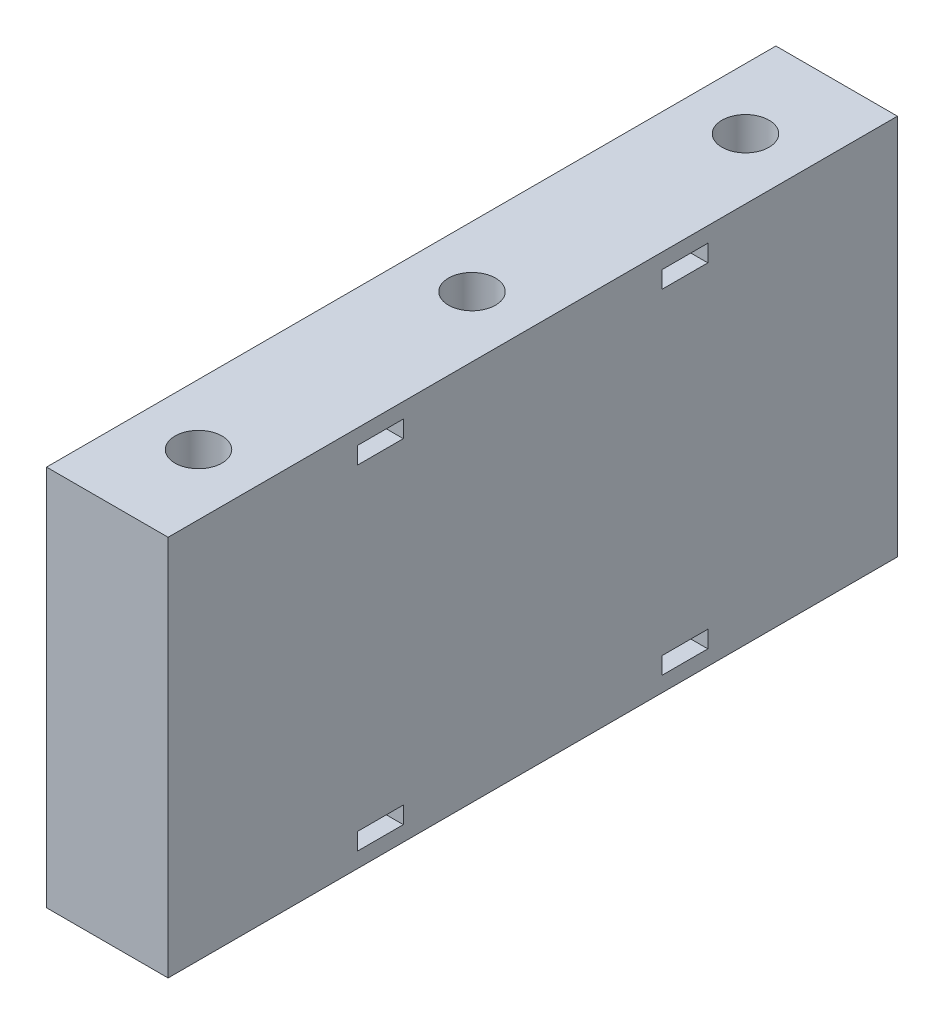
SolidWorks part; units mm, degrees
ref_plane "Front" through (0, 0, 0) normal (0, 0, 1) x (1, 0, 0)
ref_plane "Top" through (0, 0, 0) normal (0, 1, 0) x (1, 0, 0)
ref_plane "Right" through (0, 0, 0) normal (1, 0, 0) x (0, 0, -1)
sketch "Sketch1" plane through (0, 0, 0) normal (1, 0, 0) x (0, 0, -1)
  line L1 (-38.1, -19.939) -> (38.1, -19.939)
  line L2 (-38.1, -19.939) -> (-38.1, 19.939)
  line L3 (-38.1, 19.939) -> (38.1, 19.939)
  line L4 (38.1, -19.939) -> (38.1, 19.939)
  line L5 (-38.1, -19.939) -> (38.1, 19.939) construction
  line L6 (-38.1, 19.939) -> (38.1, -19.939) construction
  point P0 (0, 0)
  dimension "D1" = 39.878
  dimension "D2" = 76.2
extrude "Boss-Extrude1" add sketch "Sketch1" along normal blind 12.7
sketch "Sketch2" plane through (12.7, 0, 0) normal (1, 0, 0) x (0, 0, -1)
  line L0 (38.1, -19.939) -> (38.1, 19.939) construction
  line L1 (-18.288, 18.3515) -> (-13.5255, 18.3515)
  line L2 (-18.288, 18.3515) -> (-18.288, 16.5735)
  line L3 (-18.288, 16.5735) -> (-13.5255, 16.5735)
  line L4 (-13.5255, 18.3515) -> (-13.5255, 16.5735)
  line L5 (-18.288, 18.3515) -> (-13.5255, 16.5735) construction
  line L6 (-18.288, 16.5735) -> (-13.5255, 18.3515) construction
  line L7 (13.5255, 18.3515) -> (18.288, 18.3515)
  line L8 (13.5255, 18.3515) -> (13.5255, 16.5735)
  line L9 (13.5255, 16.5735) -> (18.288, 16.5735)
  line L10 (18.288, 18.3515) -> (18.288, 16.5735)
  line L11 (13.5255, 18.3515) -> (18.288, 16.5735) construction
  line L12 (13.5255, 16.5735) -> (18.288, 18.3515) construction
  line L13 (-18.288, -16.5735) -> (-13.5255, -16.5735)
  line L14 (-18.288, -16.5735) -> (-18.288, -18.3515)
  line L15 (-18.288, -18.3515) -> (-13.5255, -18.3515)
  line L16 (-13.5255, -16.5735) -> (-13.5255, -18.3515)
  line L17 (-18.288, -16.5735) -> (-13.5255, -18.3515) construction
  line L18 (-18.288, -18.3515) -> (-13.5255, -16.5735) construction
  line L19 (18.288, -18.3515) -> (13.5255, -18.3515)
  line L20 (18.288, -18.3515) -> (18.288, -16.5735)
  line L21 (18.288, -16.5735) -> (13.5255, -16.5735)
  line L22 (13.5255, -18.3515) -> (13.5255, -16.5735)
  line L23 (18.288, -18.3515) -> (13.5255, -16.5735) construction
  line L24 (18.288, -16.5735) -> (13.5255, -18.3515) construction
  line L25 (38.1, 19.939) -> (-38.1, 19.939) construction
  line L26 (-38.1, -19.939) -> (38.1, -19.939) construction
  line L27 (-38.1, 19.939) -> (-38.1, -19.939) construction
  point P0 (-15.9068, 17.4625)
  point P5 (15.9068, 17.4625)
  point P10 (-15.9067, -17.4625)
  point P15 (15.9068, -17.4625)
  dimension "D1" = 4.7625
  dimension "D2" = 1.778
  dimension "D3" = 19.812
  dimension "D4" = 1.5875
  dimension "D5" = 1.5875
  dimension "D6" = 19.812
extrude "Cut-Extrude1" cut sketch "Sketch2" against normal through all
sketch "Sketch5" plane through (0, 19.939, 0) normal (0, 1, 0) x (1, 0, 0)
  line L0 (12.7, -38.1) -> (0, -38.1) construction
  line L1 (12.7, 38.1) -> (0, 38.1) construction
  line L2 (6.35, -28.575) -> (6.35, 0) construction
  line L3 (6.35, 0) -> (6.35, 28.575) construction
  line L5 (6.35, 28.575) -> (0, 28.575) construction
  line L6 (0, 38.1) -> (0, -38.1) construction
  line L8 (6.35, 28.575) -> (12.7, 28.575) construction
  line L9 (12.7, 38.1) -> (12.7, -38.1) construction
  point P1 (6.35, 28.575)
  point P3 (6.35, 0)
  point P5 (6.35, -28.575)
  dimension "D1" = 9.525
  dimension "D2" = 9.525
hole_wizard "#10 (0.1935) Diameter Hole1" positions "Sketch5" profile "Sketch4" hole size "#10" standard "ANSI Inch" end condition up to next
sketch "Sketch4" plane through (6.35, 19.939, -28.575) normal (1, 0, 0) x (0, 0, 1)
  line L0 (0, 0) -> (0, 39.878)
  line L1 (0, 39.878) -> (2.4574, 39.878)
  line L2 (2.4574, 39.878) -> (2.4574, 0)
  line L5 (2.4574, 0) -> (0, 0)
  line L11 (0, -6.35) -> (0, 107.95) construction
  dimension "Thru Hole Dia." = 4.9149
  dimension "Thru Hole Depth" = 39.878
